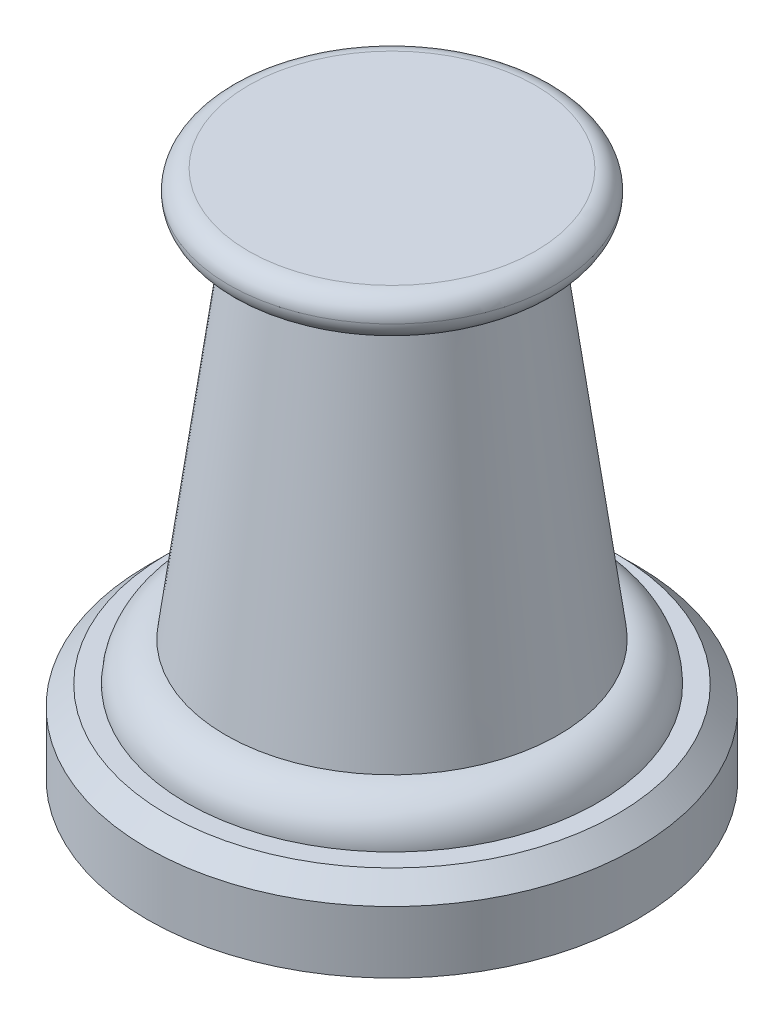
SolidWorks part; units mm, degrees
ref_plane "Front Plane" through (0, 0, 0) normal (0, 0, 1) x (1, 0, 0)
ref_plane "Top Plane" through (0, 0, 0) normal (0, 1, 0) x (1, 0, 0)
ref_plane "Right Plane" through (0, 0, 0) normal (1, 0, 0) x (0, 0, -1)
sketch "Sketch3" plane through (0, 0, 0) normal (0, 0, 1) x (1, 0, 0)
  line L0 (0, 0) -> (-9.525, 0)
  line L1 (-9.525, 0) -> (-9.525, 3.175)
  line L2 (-9.525, 3.175) -> (-8.001, 3.175)
  line L3 (-8.001, 3.175) -> (-8.001, 4.699)
  line L4 (-8.001, 4.699) -> (-6.477, 4.699)
  line L5 (-6.477, 4.699) -> (-4.572, 19.05)
  line L6 (-4.572, 19.05) -> (-6.35, 19.05)
  line L7 (-6.35, 19.05) -> (-6.35, 20.574)
  line L8 (-6.35, 20.574) -> (0, 20.574)
  line L9 (0, 20.574) -> (0, 0)
  point P0 (0, 0)
  point P1 (-9.525, 0)
  point P3 (-9.525, 3.175)
  point P4 (-8.001, 3.175)
  point P5 (-8.001, 4.699)
  point P6 (-6.477, 4.699)
  point P7 (-4.572, 19.05)
  point P8 (-6.35, 20.574)
  point P9 (0, 20.574)
  point P11 (-6.35, 19.05)
revolve "Revolve1" add sketch "Sketch3" angle 360 about L9
chamfer "Chamfer1" distance 0.762 angle 45 1 edges at (0, 3.175, 9.525)
fillet "Fillet2" radius 1.524 1 edges at (0, 4.699, 8.001)
fillet "Fillet3" radius 0.762 2 edges at (0, 20.574, 6.35) (0, 19.05, 6.35)
